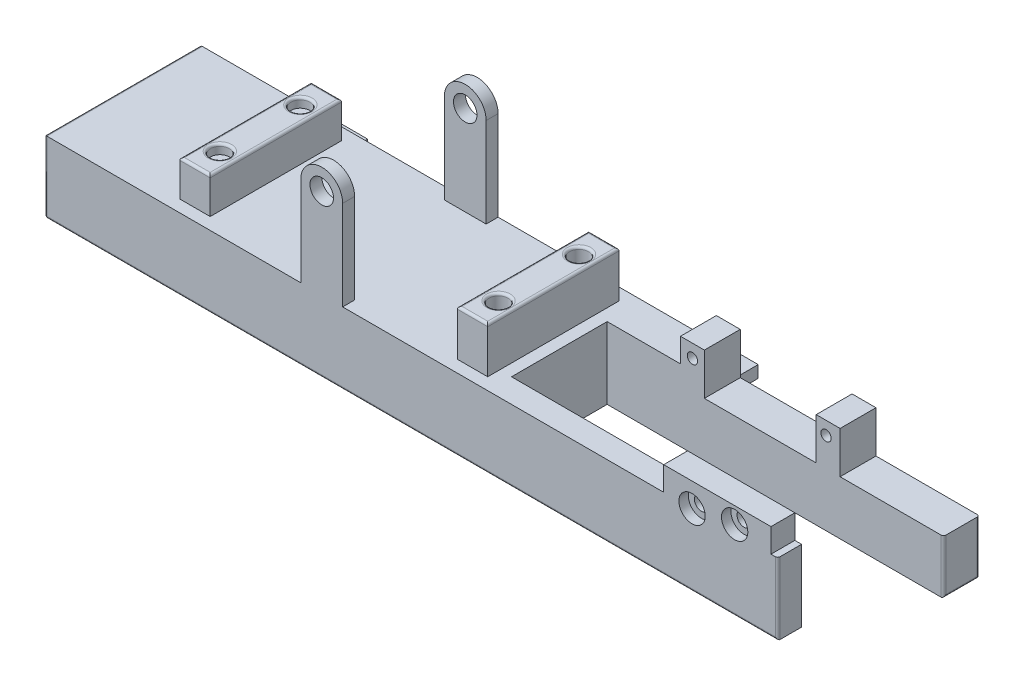
SolidWorks part; units mm, degrees
other "Markup1"
sketch "Sketch17" plane through (106.68, 38.735, 16.51) normal (0.2565, 0.8765, 0.4073) x (0.8462, 0, -0.5329)
ref_plane "Front" through (0, 0, 0) normal (0, 0, 1) x (1, 0, 0)
ref_plane "Top" through (0, 0, 0) normal (0, 1, 0) x (1, 0, 0)
ref_plane "Right" through (0, 0, 0) normal (1, 0, 0) x (0, 0, -1)
sketch "Sketch1" plane through (0, 0, 0) normal (0, 1, 0) x (1, 0, 0)
  line L0 (-58.8676, 16.51) -> (-58.8676, -16.51)
  line L1 (-106.68, 16.51) -> (106.68, 16.51)
  line L2 (-106.68, 16.51) -> (-106.68, -16.51)
  line L3 (-106.68, -16.51) -> (106.68, -16.51)
  line L4 (106.68, 16.51) -> (106.68, -16.51)
  line L5 (-106.68, 16.51) -> (106.68, -16.51) construction
  line L6 (-106.68, -16.51) -> (106.68, 16.51) construction
  line L7 (106.68, -16.51) -> (55.88, -16.51)
  line L8 (106.68, -16.51) -> (106.68, 8.89)
  line L9 (106.68, 8.89) -> (55.88, 8.89)
  line L10 (55.88, -16.51) -> (55.88, 8.89)
  line L11 (0, -55) -> (0, 55) construction
  line L12 (36.4884, 16.51) -> (46.4884, 16.51)
  line L13 (36.4884, 16.51) -> (36.4884, 29.718)
  line L14 (36.4884, 29.718) -> (46.4884, 29.718)
  line L15 (46.4884, 16.51) -> (46.4884, 29.718)
  line L16 (-36.4884, 29.718) -> (-46.4884, 29.718)
  line L17 (-46.4884, 16.51) -> (-46.4884, 29.718)
  line L18 (-36.4884, 16.51) -> (-46.4884, 16.51)
  line L19 (-36.4884, 16.51) -> (-36.4884, 29.718)
  line L21 (55.88, -16.51) -> (96.8527, -16.51)
  line L22 (55.88, -16.51) -> (55.88, -11.43)
  line L23 (55.88, -11.43) -> (96.8527, -11.43)
  line L24 (96.8527, -16.51) -> (96.8527, -11.43)
  circle A0 centre (-41.4884, 20.01) radius 2
  circle A1 centre (41.4884, 20.01) radius 2
  point P0 (0, 0)
  dimension "D7" = 4
  dimension "D1" = 213.36
  dimension "D2" = 33.02
  dimension "D3" = 25.4
  dimension "D4" = 50.8
  dimension "D5" = 10
  dimension "D6" = 13.208
  dimension "D8" = 5.08
extrude "Boss-Extrude1" add sketch "Sketch1" along normal blind 15.24 contours L3 L10 L9 L4 L1 L0 | L3 L24 L23 L10 region at (6.1788, 0, -1.1772) region at (76.3663, 0, 13.97)
sketch "Sketch3" plane through (0, 0, 16.51) normal (0, 0, 1) x (1, 0, 0)
  line L0 (4.445, 15.24) -> (-4.445, 15.24)
  line L1 (-58.8676, 15.24) -> (96.8527, 15.24) construction
  line L2 (-4.445, 15.24) -> (-4.445, 34.29)
  line L3 (4.445, 15.24) -> (4.445, 34.29)
  line L4 (0, -55) -> (0, 55) construction
  arc A0 (-4.445, 34.29) -> (4.445, 34.29) centre (0, 34.29) cw
  circle A1 centre (0, 34.29) radius 2.5
  point P8 (0, 15.24)
  dimension "D2" = 5
  dimension "D1" = 8.89
  dimension "D3" = 19.05
extrude "Boss-Extrude2" add sketch "Sketch3" against normal blind 2.54
mirror "Mirror1" about plane through (0, 0, 0) normal (0, 0, 1) of "Boss-Extrude2"
sketch "Sketch4" plane through (0, 15.24, 0) normal (0, 1, 0) x (1, 0, 0)
  line L0 (-55, 0) -> (55, 0) construction
  line L1 (26.2471, 13.9568) -> (32.7047, 13.9568)
  line L2 (26.2471, 13.9568) -> (26.2471, -13.9568)
  line L3 (26.2471, -13.9568) -> (32.7047, -13.9568)
  line L4 (32.7047, 13.9568) -> (32.7047, -13.9568)
  line L5 (0, -55) -> (0, 55) construction
  line L6 (-26.2471, -13.9568) -> (-32.7047, -13.9568)
  line L7 (-32.7047, 13.9568) -> (-32.7047, -13.9568)
  line L8 (-26.2471, 13.9568) -> (-32.7047, 13.9568)
  line L9 (-26.2471, 13.9568) -> (-26.2471, -13.9568)
  point P4 (26.2471, 0)
extrude "Boss-Extrude3" add sketch "Sketch4" along normal blind 7.62
sketch "Sketch11" plane through (0, 22.86, 0) normal (0, 1, 0) x (1, 0, 0)
  line L4 (-32.7047, -13.9568) -> (-26.2471, -13.9568)
  line L5 (-32.7047, 13.9568) -> (-32.7047, -13.9568)
  line L6 (-26.2471, 13.9568) -> (-32.7047, 13.9568)
  line L7 (-26.2471, -13.9568) -> (-26.2471, 13.9568)
  line L8 (-32.7047, -13.9568) -> (-26.2471, -13.9568)
  line L9 (-32.7047, 13.9568) -> (-32.7047, -13.9568)
  line L10 (-26.2471, 13.9568) -> (-32.7047, 13.9568)
  line L11 (-26.2471, -13.9568) -> (-26.2471, 13.9568)
  line L12 (32.7047, 13.9568) -> (26.2471, 13.9568)
  line L13 (32.7047, -13.9568) -> (32.7047, 13.9568)
  line L14 (26.2471, -13.9568) -> (32.7047, -13.9568)
  line L15 (26.2471, 13.9568) -> (26.2471, -13.9568)
  line L16 (32.7047, 13.9568) -> (26.2471, 13.9568)
  line L17 (32.7047, -13.9568) -> (32.7047, 13.9568)
  line L18 (26.2471, -13.9568) -> (32.7047, -13.9568)
  line L19 (26.2471, 13.9568) -> (26.2471, -13.9568)
  dimension "D1" = 0
  dimension "D2" = 0
extrude "Boss-Extrude6" add sketch "Sketch11" along normal blind 2.0955 contours L16 L19 L18 L17
sketch "Sketch6" plane through (0, 22.86, 0) normal (0, 1, 0) x (1, 0, 0)
  line L0 (-55, 0) -> (55, 0) construction
  line L1 (0, -55) -> (0, 55) construction
  line L4 (-26.2471, -13.9568) -> (-26.2471, 13.9568)
  line L5 (-26.2471, 13.9568) -> (-32.7047, 13.9568)
  line L6 (-32.7047, 13.9568) -> (-32.7047, -13.9568)
  line L7 (-32.7047, -13.9568) -> (-26.2471, -13.9568)
  line L8 (-26.2471, -13.9568) -> (-26.2471, 13.9568)
  line L9 (-26.2471, 13.9568) -> (-32.7047, 13.9568)
  line L10 (-32.7047, 13.9568) -> (-32.7047, -13.9568)
  line L11 (-32.7047, -13.9568) -> (-26.2471, -13.9568)
  circle A0 centre (-29.5986, 8.5505) radius 2
  circle A1 centre (-29.5986, -8.5505) radius 2
  circle A2 centre (29.5986, -8.5505) radius 2
  circle A3 centre (29.5986, 8.5505) radius 2
  dimension "D3" = 4
  dimension "D1" = 0
extrude "Cut-Extrude1" cut sketch "Sketch6" against normal blind 2.032 and the other way through all contours A3 | A2 | A1 | A0 | A0 | A1 region at (-29.5986, 22.86, -8.5505) region at (-29.5986, 22.86, 8.5505) region at (29.5986, 22.86, 8.5505) region at (29.5986, 22.86, -8.5505)
fillet "Fillet1" radius 0.508 22 edges at (-58.8676, 15.24, 0) (-58.8676, 0, 0) (106.68, 0, -12.7) (106.68, 7.62, -8.89) (106.68, 7.62, -16.51) (-58.8676, 7.62, -16.51) (-58.8676, 7.62, 16.51) (18.9925, 0, 16.51) (-29.5986, 22.86, -10.5505) (-29.5986, 22.86, 6.5505) (-29.4759, 22.86, 13.9568) (-32.7047, 22.86, 0) (-29.4759, 22.86, -13.9568) (-26.2471, 22.86, 0) (29.5986, 24.9555, 10.5505) (29.5986, 24.9555, -6.5505) (29.4759, 24.9555, 13.9568) (26.2471, 24.9555, 0) (29.4759, 24.9555, -13.9568) (32.7047, 24.9555, 0) (106.68, 15.24, -12.7) (96.8527, 7.62, 16.51)
sketch "Sketch8" plane through (0, 15.24, 0) normal (0, 1, 0) x (1, 0, 0)
  line L1 (58.1514, 8.382) -> (58.1514, -16.002)
  line L3 (56.8238, 8.89) -> (35.2338, 8.89)
  line L4 (56.8238, 8.89) -> (56.8238, -11.43)
  line L5 (56.8238, -11.43) -> (35.2338, -11.43)
  line L6 (35.2338, 8.89) -> (35.2338, -11.43)
  line M44 (55.88, -11.43) -> (55.88, 8.89)
  line M46 (96.8527, -11.43) -> (55.88, -11.43)
  dimension "D1" = 20.32
  dimension "D3" = 21.59
extrude "Cut-Extrude2" cut sketch "Sketch8" against normal through all contours L3 L6 L5 L4 M46 M44 region at (45.5569, 15.24, 1.27)
extrude "Boss-Extrude5" add sketch "Sketch1<3>" along normal blind 2.54 contours L1 L15 L14 L13 | L1 L19 L16 L17 region at (-41.4884, 0, -23.4404) region at (41.4884, 0, -23.4404)
sketch "Sketch1<3>" plane through (0, 0, 0) normal (0, 1, 0) x (1, 0, 0) same geometry as "Sketch1"
sketch "Sketch14" plane through (0, 0, -8.89) normal (0, 0, 1) x (1, 0, 0)
  line L0 (106.172, 15.24) -> (35.2338, 15.24) construction
  line L2 (106.68, 15.24) -> (106.68, 11.43)
  line L3 (106.68, 11.43) -> (55.88, 11.43)
  line L4 (55.88, 15.24) -> (55.88, 11.43)
  line L5 (106.68, 14.732) -> (106.68, 0.508) construction
  line L6 (55.88, 15.24) -> (106.68, 15.24)
  dimension "D1" = 3.81
  dimension "D4" = 50.8
extrude "Cut-Extrude5" cut sketch "Sketch14" against normal through all and the other way blind 9.2075
sketch "Sketch15" plane through (0, 0, -8.89) normal (0, 0, 1) x (1, 0, 0)
  line L0 (55.88, 15.24) -> (35.2338, 15.24) construction
  line L1 (50.8, 15.24) -> (55.88, 15.24)
  line L2 (50.8, 15.24) -> (50.8, 20.32)
  line L3 (50.8, 20.32) -> (55.88, 20.32)
  line L4 (55.88, 15.24) -> (55.88, 20.32)
  line L5 (106.172, 11.43) -> (55.88, 11.43) construction
  line L6 (79.629, 11.43) -> (84.709, 11.43)
  line L7 (79.629, 11.43) -> (79.629, 20.32)
  line L8 (79.629, 20.32) -> (84.709, 20.32)
  line L9 (84.709, 11.43) -> (84.709, 20.32)
  line L11 (55.88, 11.43) -> (55.88, 15.24) construction
  dimension "D1" = 5.08
  dimension "D2" = 23.749
  dimension "D3" = 5.08
  dimension "D4" = 5.08
extrude "Boss-Extrude7" add sketch "Sketch15" against normal up to vertex (7.62 mm away) up to point (55.88, 15.24, -16.51)
sketch "Sketch16" plane through (0, 0, -8.89) normal (0, 0, 1) x (1, 0, 0)
  line L0 (55.88, 11.43) -> (55.88, 20.32) construction
  line L1 (106.172, 11.43) -> (84.709, 11.43) construction
  circle A0 centre (53.34, 17.526) radius 1.0922
  circle A1 centre (81.7245, 17.526) radius 1.0922
  dimension "D1" = 2.1844
  dimension "D2" = 2.54
  dimension "D3" = 6.096
  dimension "D4" = 28.3845
extrude "Cut-Extrude6" cut sketch "Sketch16" against normal up to next
sketch "Sketch18" plane through (0, 15.24, 0) normal (0, 1, 0) x (1, 0, 0)
  line L0 (35.2338, -11.43) -> (96.8527, -11.43) construction
  line L1 (95.4237, -11.43) -> (72.6409, -11.43)
  line L2 (95.4237, -11.43) -> (95.4237, -16.51)
  line L3 (95.4237, -16.51) -> (72.6409, -16.51)
  line L4 (72.6409, -11.43) -> (72.6409, -16.51)
  line L5 (4.445, -16.51) -> (96.3447, -16.51) construction
extrude "Boss-Extrude8" add sketch "Sketch18" along normal blind 5.08
sketch "Sketch9" plane through (0, 0, 11.43) normal (0, 0, -1) x (-1, 0, 0)
  line L0 (-87.7134, 16.8367) -> (-78.6583, 15.24) construction
  line L2 (25.4254, 0) -> (-25.4254, 0) construction
  circle A0 centre (-87.7134, 16.8367) radius 1.4986
  circle A1 centre (-78.6583, 15.24) radius 1.4986
  point P4 (-78.2343, 11.9417)
  point P5 (-78.6583, 10.5965)
  dimension "D1" = 2.9972
  dimension "D4" = 15.24
  dimension "D2" = 9.1948
  dimension "D3" = 10
extrude "Cut-Extrude3" cut sketch "Sketch9" along normal blind 12.7 and the other way blind 12.7
sketch "Sketch10" plane through (0, 0, 16.51) normal (0, 0, 1) x (1, 0, 0)
  circle A0 centre (78.6583, 15.24) radius 2.794
  circle A1 centre (87.7134, 16.8367) radius 2.794
  circle M2 centre (87.7134, 16.8367) radius 1.4986
  circle M3 centre (78.6583, 15.24) radius 1.4986
  dimension "D1" = 5.588
extrude "Cut-Extrude4" cut sketch "Sketch10" against normal blind 2 contours A0 M3 | A1 M2 region at (75.9434, 15.24, 16.51) region at (84.9985, 16.8367, 16.51)
